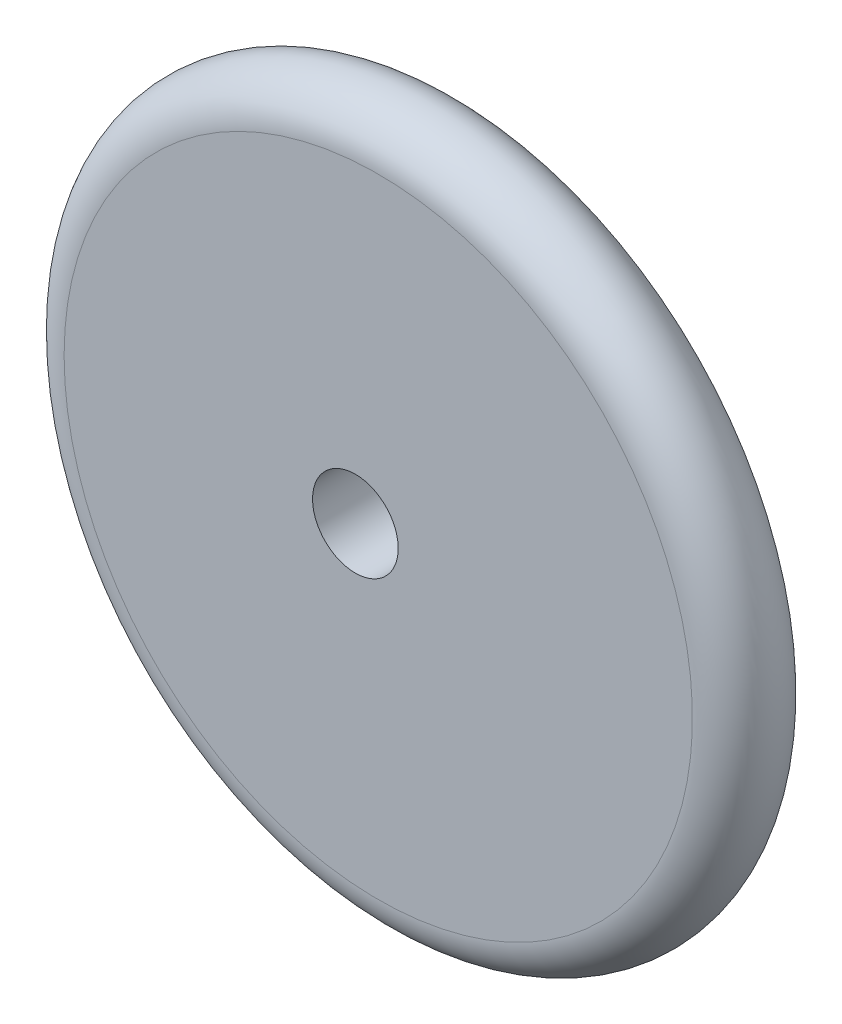
SolidWorks part; units mm, degrees
ref_plane "Front Plane" through (0, 0, 0) normal (0, 0, 1) x (1, 0, 0)
ref_plane "Top Plane" through (0, 0, 0) normal (0, 1, 0) x (1, 0, 0)
ref_plane "Right Plane" through (0, 0, 0) normal (1, 0, 0) x (0, 0, -1)
sketch "Sketch6" plane through (0, 0, 0) normal (0, 1, 0) x (1, 0, 0)
  line L0 (8.0204, 74.6018) -> (118.0204, 74.6018)
  line L1 (8.0204, 74.6018) -> (8.0204, 44.6018)
  line L2 (8.0204, 44.6018) -> (118.0204, 44.6018)
  arc A0 (118.0204, 44.6018) -> (118.0204, 74.6018) centre (118.0204, 59.6018) ccw
revolve "Revolve3" add sketch "Sketch6" angle 360 about L1
sketch "Sketch7" plane through (0, 0, 0) normal (0, 0, 1) x (1, 0, 0)
  circle A0 centre (0, 0) radius 15
  dimension "D1" = 30
extrude "Cut-Extrude1" cut sketch "Sketch7" against normal through all
